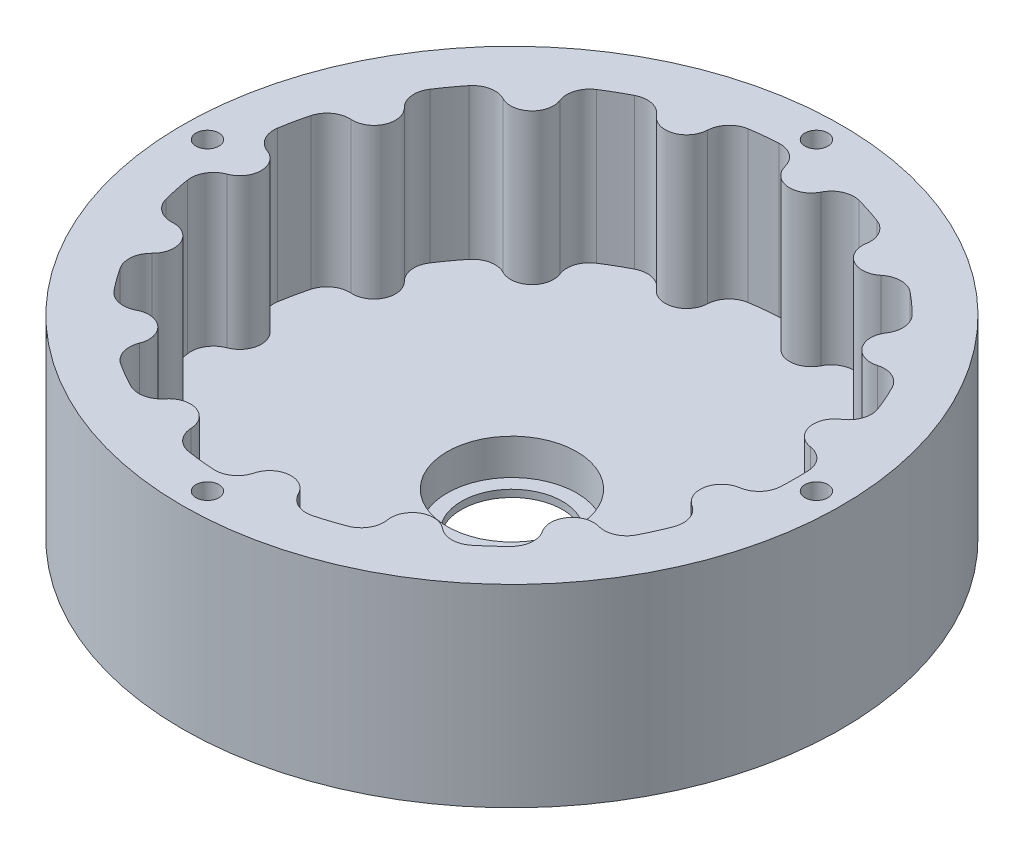
SolidWorks part; units mm, degrees
ref_plane "Front Plane" through (0, 0, 0) normal (0, 0, 1) x (1, 0, 0)
ref_plane "Top Plane" through (0, 0, 0) normal (0, 1, 0) x (1, 0, 0)
ref_plane "Right Plane" through (0, 0, 0) normal (1, 0, 0) x (0, 0, -1)
sketch "Sketch1" plane through (0, 0, 0) normal (0, 1, 0) x (1, 0, 0)
  line L0 (0, 0) -> (-38, 0) construction
  line L1 (-38.6368, 8.2125) -> (0, 0) construction
  circle A0 centre (0, 0) radius 46
  arc A1 (-36.9604, -2.8141) -> (-36.9604, 2.8141) centre (-38, 0) ccw
  arc A2 (-36.9604, 2.8141) -> (-38.9946, 6.2987) centre (-35.8602, 5.7924) cw
  arc A3 (-38.9946, 6.2987) -> (-38.6368, 8.2125) centre (0, 0) cw
  arc A4 (-38.9946, -6.2987) -> (-38.6368, -8.2125) centre (0, 0) ccw
  arc A5 (-36.9604, -2.8141) -> (-38.9946, -6.2987) centre (-35.8602, -5.7924) ccw
  arc A6 (-38.1852, 10.1064) -> (-38.6368, 8.2125) centre (0, 0) ccw
  arc A7 (-34.9096, 12.4623) -> (-38.1852, 10.1064) centre (-35.1159, 9.294) ccw
  arc A8 (-34.9096, 12.4623) -> (-32.6204, 17.604) centre (-34.7147, 15.456) ccw
  arc A9 (-32.6204, 17.604) -> (-33.0614, 21.6147) centre (-30.4039, 19.8773) cw
  arc A10 (-33.0614, 21.6147) -> (-31.9562, 23.2175) centre (0, 0) cw
  arc A11 (-30.7733, 24.764) -> (-31.9562, 23.2175) centre (0, 0) ccw
  arc A12 (-26.8226, 25.5839) -> (-30.7733, 24.764) centre (-28.2997, 22.7734) ccw
  arc A13 (-26.8226, 25.5839) -> (-22.64, 29.35) centre (-25.427, 28.2395) ccw
  arc A14 (-22.64, 29.35) -> (-21.4116, 33.1933) centre (-19.6906, 30.5252) cw
  arc A15 (-21.4116, 33.1933) -> (-19.75, 34.208) centre (0, 0) cw
  arc A16 (-18.0404, 35.1396) -> (-19.75, 34.208) centre (0, 0) ccw
  arc A17 (-14.0978, 34.2818) -> (-18.0404, 35.1396) centre (-16.5903, 32.3151) ccw
  arc A18 (-14.0978, 34.2818) -> (-8.745, 36.0211) centre (-11.7426, 36.1401) ccw
  arc A19 (-8.745, 36.0211) -> (-6.0596, 39.0324) centre (-5.5725, 35.895) cw
  arc A20 (-6.0596, 39.0324) -> (-4.1289, 39.2836) centre (0, 0) cw
  arc A21 (-2.1881, 39.4393) -> (-4.1289, 39.2836) centre (0, 0) ccw
  arc A22 (1.0647, 37.0521) -> (-2.1881, 39.4393) centre (-2.0123, 36.2692) ccw
  arc A23 (1.0647, 37.0521) -> (6.6621, 36.4638) centre (3.9721, 37.7918) ccw
  arc A24 (6.6621, 36.4638) -> (10.3402, 38.1226) centre (9.5091, 35.0583) cw
  arc A25 (10.3402, 38.1226) -> (12.2062, 37.5667) centre (0, 0) cw
  arc A26 (14.0425, 36.9196) -> (12.2062, 37.5667) centre (0, 0) ccw
  arc A27 (16.0431, 33.4157) -> (14.0425, 36.9196) centre (12.9137, 33.952) ccw
  arc A28 (16.0431, 33.4157) -> (20.9173, 30.6016) centre (19, 32.909) ccw
  arc A29 (20.9173, 30.6016) -> (24.9521, 30.6209) centre (22.9465, 28.1596) cw
  arc A30 (24.9521, 30.6209) -> (26.4307, 29.3542) centre (0, 0) cw
  arc A31 (27.845, 28.0162) -> (26.4307, 29.3542) centre (0, 0) ccw
  arc A32 (28.2475, 24.0015) -> (27.845, 28.0162) centre (25.6068, 25.7642) ccw
  arc A33 (28.2475, 24.0015) -> (31.5557, 19.4481) centre (30.7426, 22.3358) ccw
  arc A34 (31.5557, 19.4481) -> (35.2495, 17.8247) centre (32.4162, 16.3919) cw
  arc A35 (35.2495, 17.8247) -> (36.085, 16.0661) centre (0, 0) cw
  arc A36 (36.8329, 14.2685) -> (36.085, 16.0661) centre (0, 0) ccw
  arc A37 (35.5677, 10.4371) -> (36.8329, 14.2685) centre (33.8723, 13.1216) ccw
  arc A38 (35.5677, 10.4371) -> (36.7378, 4.9319) centre (37.1696, 7.9006) ccw
  arc A39 (36.7378, 4.9319) -> (39.452, 1.9464) centre (36.2809, 1.7899) cw
  arc A40 (39.452, 1.9464) -> (39.5, 0) centre (0, 0) cw
  arc A41 (39.452, -1.9464) -> (39.5, 0) centre (0, 0) ccw
  arc A42 (36.7378, -4.9319) -> (39.452, -1.9464) centre (36.2809, -1.7899) ccw
  arc A43 (36.7378, -4.9319) -> (35.5677, -10.4371) centre (37.1696, -7.9006) ccw
  arc A44 (35.5677, -10.4371) -> (36.8329, -14.2685) centre (33.8723, -13.1216) cw
  arc A45 (36.8329, -14.2685) -> (36.085, -16.0661) centre (0, 0) cw
  arc A46 (35.2495, -17.8247) -> (36.085, -16.0661) centre (0, 0) ccw
  arc A47 (31.5557, -19.4481) -> (35.2495, -17.8247) centre (32.4162, -16.3919) ccw
  arc A48 (31.5557, -19.4481) -> (28.2475, -24.0015) centre (30.7426, -22.3358) ccw
  arc A49 (28.2475, -24.0015) -> (27.845, -28.0162) centre (25.6068, -25.7642) cw
  arc A50 (27.845, -28.0162) -> (26.4307, -29.3542) centre (0, 0) cw
  arc A51 (24.9521, -30.6209) -> (26.4307, -29.3542) centre (0, 0) ccw
  arc A52 (20.9173, -30.6016) -> (24.9521, -30.6209) centre (22.9465, -28.1596) ccw
  arc A53 (20.9173, -30.6016) -> (16.0431, -33.4157) centre (19, -32.909) ccw
  arc A54 (16.0431, -33.4157) -> (14.0425, -36.9196) centre (12.9137, -33.952) cw
  arc A55 (14.0425, -36.9196) -> (12.2062, -37.5667) centre (0, 0) cw
  arc A56 (10.3402, -38.1226) -> (12.2062, -37.5667) centre (0, 0) ccw
  arc A57 (6.6621, -36.4638) -> (10.3402, -38.1226) centre (9.5091, -35.0583) ccw
  arc A58 (6.6621, -36.4638) -> (1.0647, -37.0521) centre (3.9721, -37.7918) ccw
  arc A59 (1.0647, -37.0521) -> (-2.1881, -39.4393) centre (-2.0123, -36.2692) cw
  arc A60 (-2.1881, -39.4393) -> (-4.1289, -39.2836) centre (0, 0) cw
  arc A61 (-6.0596, -39.0324) -> (-4.1289, -39.2836) centre (0, 0) ccw
  arc A62 (-8.745, -36.0211) -> (-6.0596, -39.0324) centre (-5.5725, -35.895) ccw
  arc A63 (-8.745, -36.0211) -> (-14.0978, -34.2818) centre (-11.7426, -36.1401) ccw
  arc A64 (-14.0978, -34.2818) -> (-18.0404, -35.1396) centre (-16.5903, -32.3151) cw
  arc A65 (-18.0404, -35.1396) -> (-19.75, -34.208) centre (0, 0) cw
  arc A66 (-21.4116, -33.1933) -> (-19.75, -34.208) centre (0, 0) ccw
  arc A67 (-22.64, -29.35) -> (-21.4116, -33.1933) centre (-19.6906, -30.5252) ccw
  arc A68 (-22.64, -29.35) -> (-26.8226, -25.5839) centre (-25.427, -28.2395) ccw
  arc A69 (-26.8226, -25.5839) -> (-30.7733, -24.764) centre (-28.2997, -22.7734) cw
  arc A70 (-30.7733, -24.764) -> (-31.9562, -23.2175) centre (0, 0) cw
  arc A71 (-33.0614, -21.6147) -> (-31.9562, -23.2175) centre (0, 0) ccw
  arc A72 (-32.6204, -17.604) -> (-33.0614, -21.6147) centre (-30.4039, -19.8773) ccw
  arc A73 (-32.6204, -17.604) -> (-34.9096, -12.4623) centre (-34.7147, -15.456) ccw
  arc A74 (-34.9096, -12.4623) -> (-38.1852, -10.1064) centre (-35.1159, -9.294) cw
  arc A75 (-38.1852, -10.1064) -> (-38.6368, -8.2125) centre (0, 0) cw
  dimension "D1" = 92
  dimension "D3" = 3
  dimension "D4" = 39.5
  dimension "D5" = 3.175
  dimension "D2" = 38
  dimension "D6" = 12
  dimension "D7" = 15
extrude "Boss-Extrude1" add sketch "Sketch1" along normal blind 27 contours A0 A74 A75 A4 A5 A1 A2 A3 A6 A7 A8 A9 A10 A11 A12 A13 A14 A15 A16 A17 A18 A19 A20 A21 A22 A23 A24 A25 A26 A27 A28 A29 A30 A31 A32 A33 A34 A35 A36 A37 A38 A39 A40 A41 A42 A43 A44 A45 A46 A47 region at (-44.6989, 0, 0)
extrude "Boss-Extrude2" add sketch "Sketch1<3>" along normal blind 6 contours A0 A74 A75 A4 A5 A1 A2 A3 A6 A7 A8 A9 A10 A11 A12 A13 A14 A15 A16 A17 A18 A19 A20 A21 A22 A23 A24 A25 A26 A27 A28 A29 A30 A31 A32 A33 A34 A35 A36 A37 A38 A39 A40 A41 A42 A43 A44 A45 A46 A47 | A75 A74 A73 A72 A71 A70 A69 A68 A67 A66 A65 A64 A63 A62 A61 A60 A59 A58 A57 A56 A55 A54 A53 A52 A51 A50 A49 A48 A47 A46 A45 A44 A43 A42 A41 A40 A39 A38 A37 A36 A35 A34 A33 A32 A31 A30 A29 A28 A27 A26 A25 region at (-44.6989, 0, 0) region at (0, 0, 0)
sketch "Sketch1<3>" plane through (0, 0, 0) normal (0, 1, 0) x (1, 0, 0) same geometry as "Sketch1"
sketch "Sketch2" plane through (0, 0, 0) normal (0, 1, 0) x (1, 0, 0)
  circle A0 centre (0, 0) radius 9.05
  circle A1 centre (0, 0) radius 7.05
  dimension "D1" = 18.1
extrude "Cut-Extrude1" cut sketch "Sketch2" along normal through all contours A1 region at (0, 0, 0)
extrude "Cut-Extrude2" cut sketch "Sketch2<3>" along normal through all from offset 1 contours A0 A1 region at (-8.794, 0, 0)
sketch "Sketch2<3>" plane through (0, 0, 0) normal (0, 1, 0) x (1, 0, 0) same geometry as "Sketch2"
hole_wizard "M3 Clearance Hole1" positions "Sketch4" profile "Sketch6" hole size "M3" standard "ANSI Metric" end condition through all
sketch "Sketch4" plane through (0, 27, 0) normal (0, 1, 0) x (1, 0, 0)
  line L2 (-42.5, 0) -> (0, 0) construction
  point P10 (-42.5, 0)
  dimension "D1" = 42.5
sketch "Sketch6" plane through (-42.5, 27, 0) normal (1, 0, 0) x (0, 0, 1)
  line L0 (0, 0) -> (0, 27)
  line L1 (0, 27) -> (1.6, 27)
  line L2 (1.6, 27) -> (1.6, 0)
  line L5 (1.6, 0) -> (0, 0)
  line L11 (0, -6.35) -> (0, 107.95) construction
  dimension "Thru Hole Dia." = 3.2
  dimension "Thru Hole Depth" = 27
pattern_circular "CirPattern1" count 4 over 360 about axis through (0, 27, 0) along (0, -1, 0) of "M3 Clearance Hole1" reverse direction yes
equation "\"Ratio\"= 15"
equation "\"Hull Diameter\"= 92"
equation "\"Fixed Ring Diameter\"= 76"
equation "\"Fixed Pin Diameter\"= 6"
equation "\"Output Ring Diameter\"= 40"
equation "\"Output Pin Diameter\"= 6"
equation "\"Disk Bearing Inner Diameter\"= 9"
equation "\"Disk Bearing Outer Diameter\"= 17"
equation "\"Disk Bearing Height\"= 5"
equation "\"Shaft Bearing Inner Diameter\"= 15"
equation "\"Shaft Bearing Outer Diameter\"= 21"
equation "\"Shaft Bearing Height\"= 4"
equation "\"Eccentricity\"= 1.5"
equation "\"Disk Height\"= 8"
equation "\"Disk Spacing\"= 5"
equation "\"Hull Height\"= 40"
equation "\"Shaft End Bearing Inner Diameter\"= 12"
equation "\"Shaft End Bearing Outer Diameter\"= 18"
equation "\"Shaft End Bearing Height\"= 4"
equation "\"Output Bearing Inner Diameter\"= 55"
equation "\"Output Bearing Outer Diameter\"= 72"
equation "\"Outer Bearing Height\"= 9"
equation "\"D1@Sketch1\"=\"Hull Diameter\""
equation "\"D3@Sketch1\"=\"Fixed Pin Diameter\"/2"
equation "\"D2@Sketch1\"=\"Fixed Ring Diameter\"/2"
equation "\"D4@Sketch1\"=(\"Fixed Ring Diameter\"/2)+(\"Eccentricity\")"
equation "\"D6@Sketch1\"=180/(\"Ratio\")"
equation "\"D7@Sketch1\"=\"Ratio\""
equation "\"D1@Sketch2\"=\"Shaft End Bearing Outer Diameter\"+0.1"
